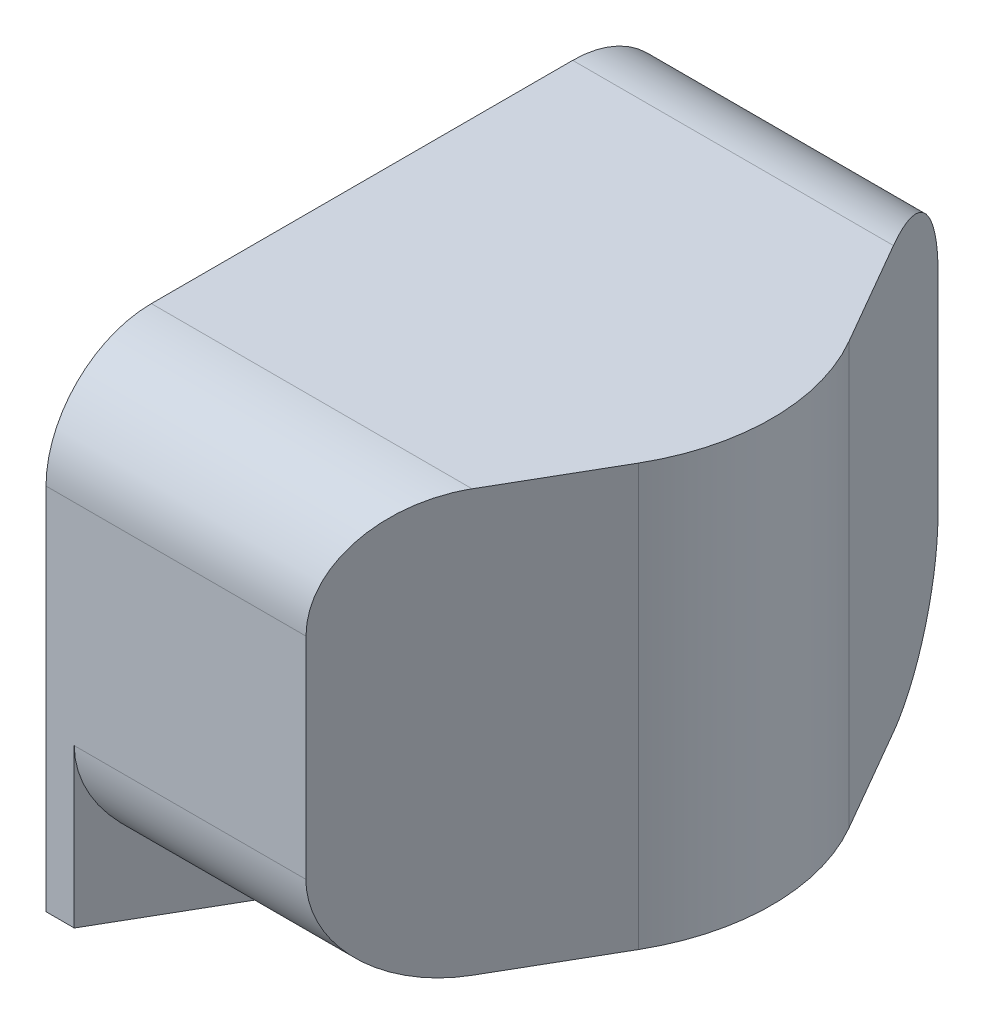
SolidWorks part; units mm, degrees
ref_plane "Front Plane" through (0, 0, 0) normal (0, 0, 1) x (1, 0, 0)
ref_plane "Top Plane" through (0, 0, 0) normal (0, 1, 0) x (1, 0, 0)
ref_plane "Right Plane" through (0, 0, 0) normal (1, 0, 0) x (0, 0, -1)
sketch "Sketch1" plane through (0, 0, 0) normal (1, 0, 0) x (0, 0, -1)
  line L1 (-3, -2) -> (3, -2)
  line L2 (-3, -2) -> (-3, 2)
  line L3 (-3, 2) -> (3, 2)
  line L4 (3, -2) -> (3, 2)
  line L5 (-3, -2) -> (3, 2) construction
  line L6 (-3, 2) -> (3, -2) construction
  point P0 (0, 0)
  dimension "D1" = 4
  dimension "D2" = 6
extrude "Boss-Extrude1" add sketch "Sketch1" against normal blind 4.2 from offset 23
sketch "Sketch2" plane through (0, 0, 0) normal (0, 1, 0) x (1, 0, 0)
  line L0 (0, 0) -> (23, 0) construction
  line L1 (22.4226, 1) -> (11.5, 19.9186)
  line L2 (11.5, 19.9186) -> (-11.5, 19.9186)
  line L3 (-11.5, 19.9186) -> (-23, 0)
  line L4 (-23, 0) -> (-11.5, -19.9186)
  line L5 (-11.5, -19.9186) -> (11.5, -19.9186)
  line L6 (11.5, -19.9186) -> (22.4226, -1)
  line L7 (11.5, 19.9186) -> (23, 19.9186)
  line L8 (23, 19.9186) -> (23, -19.9186)
  line L9 (23, -19.9186) -> (11.5, -19.9186)
  circle A0 centre (0, 0) radius 19.9186 construction
  arc A1 (22.4226, 1) -> (22.4226, -1) centre (20.6906, 0) cw
  dimension "D2" = 2
  dimension "D1" = 23
extrude "Cut-Extrude1" cut sketch "Sketch2" along normal through all both and the other way through all contours L1 A1 L6 L9 L8 L7 region at (17.3204, 0, -10.6666)
sketch "Sketch4" plane through (18.8, 0, 0) normal (-1, 0, 0) x (0, 0, 1)
  line L0 (-4, 3) -> (-4, -3)
  line L1 (-4, -3) -> (4, -3)
  line L2 (4, -3) -> (4, 3)
  line L3 (4, 3) -> (-4, 3)
  line L4 (-3, 2) -> (-3, -2)
  line L5 (-3, -2) -> (3, -2)
  line L6 (3, -2) -> (3, 2)
  line L7 (3, 2) -> (-3, 2)
  line L8 (-3, 2) -> (-3, -2)
  line L9 (-3, -2) -> (3, -2)
  line L10 (3, -2) -> (3, 2)
  line L11 (3, 2) -> (-3, 2)
  dimension "D1" = 0
  dimension "D2" = 1
sketch "Sketch5" plane through (0, 0, 0) normal (0, 1, 0) x (1, 0, 0)
  line L0 (0, 0) -> (20.8, 0) construction
  line L1 (20.8, 0) -> (19.0679, 3)
  line L2 (10.4, 18.0133) -> (-10.4, 18.0133)
  line L3 (-10.4, 18.0133) -> (-20.8, 0)
  line L4 (-20.8, 0) -> (-10.4, -18.0133)
  line L5 (-10.4, -18.0133) -> (10.4, -18.0133)
  line L6 (10.4, -18.0133) -> (15.6, -9.0067)
  line L7 (15.6, 9.0067) -> (10.4, 18.0133)
  line L10 (18.8, 3) -> (18.8, -3)
  line L11 (19.0679, -3) -> (20.8, 0)
  line L17 (22.4226, 1) -> (21.2679, 3)
  line L18 (21.2679, 3) -> (18.8, 3)
  line L19 (18.8, 3) -> (18.8, -3)
  line L20 (18.8, -3) -> (21.2679, -3)
  line L21 (21.2679, -3) -> (22.4226, -1)
  line L22 (22.4226, 1) -> (21.2679, 3)
  line L23 (21.2679, 3) -> (18.8, 3)
  line L24 (18.8, 3) -> (18.8, -3)
  line L25 (18.8, -3) -> (21.2679, -3)
  line L26 (21.2679, -3) -> (22.4226, -1)
  circle A0 centre (0, 0) radius 18.0133 construction
  arc A2 (22.4226, -1) -> (22.4226, 1) centre (20.6906, 0) ccw
  arc A3 (22.4226, -1) -> (22.4226, 1) centre (20.6906, 0) ccw
  dimension "D1" = 20.8
  dimension "D2" = 0
extrude "Boss-Extrude3" add sketch "Sketch5" along normal blind 2 and the other way blind 2.5 contours L10 L6 L1 region at (19.4772, 0, 0)
fillet "Fillet2" radius 1 4 edges at (20.034, 2, -3) (20.1679, -2, -3) (20.1679, -2, 3) (20.034, 2, 3)
